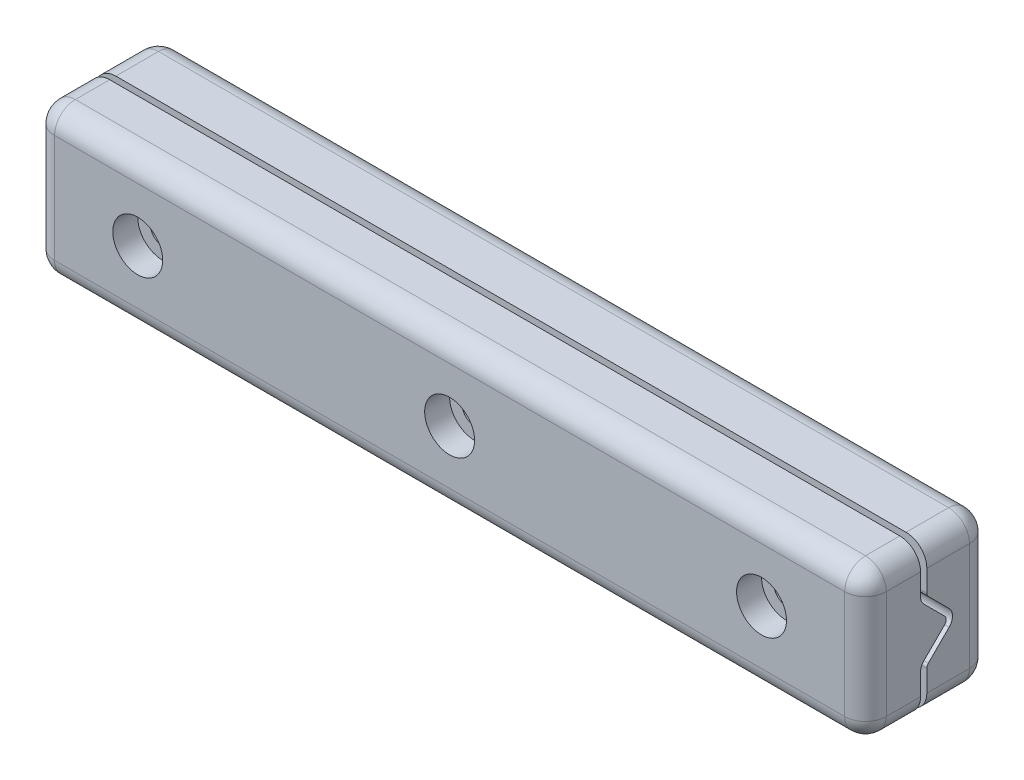
SolidWorks part; units mm, degrees
ref_plane "Спереди" through (0, 0, 0) normal (0, 0, 1) x (1, 0, 0)
ref_plane "Сверху" through (0, 0, 0) normal (0, 1, 0) x (1, 0, 0)
ref_plane "Справа" through (0, 0, 0) normal (1, 0, 0) x (0, 0, -1)
sketch "Эскиз1" plane through (0, 0, -1) normal (0, 0, 1) x (1, 0, 0)
  line L1 (303, -18) -> (503, -18)
  line L2 (303, -18) -> (303, 18)
  line L3 (303, 18) -> (503, 18)
  line L4 (503, -18) -> (503, 18)
  line L5 (403, 18) -> (403, -18) construction
  line L6 (303, 0) -> (503, 0) construction
  line L8 (500, 8.2426) -> (500, 15) construction
  line L9 (-460, 15) -> (500, 15) construction
  point P0 (403, 0)
  dimension "D3" = 200
  dimension "D1" = 3
  dimension "D2" = 3
extrude "Бобышка-Вытянуть1" add sketch "Эскиз1" along normal mid plane 30
fillet "Скругление1" radius 5 12 edges at (403, -18, -16) (303, -18, -1) (303, 0, -16) (503, -18, -1) (503, 0, -16) (403, -18, 14) (303, 0, 14) (503, 0, 14) (503, 18, -1) (403, 18, 14) (303, 18, -1) (403, 18, -16)
sketch "Эскиз3" plane through (503, 0, 0) normal (1, 0, 0) x (0, 0, -1)
  line L54 (0.0555, 5.8839) -> (5.0555, 0.8839)
  line L55 (5.0555, -0.8839) -> (0.0555, -5.8839)
  line L56 (-0.75, -7.8284) -> (-0.75, -15)
  line L57 (-0.75, -15) -> (0.75, -15)
  line L58 (0.75, -15) -> (0.75, -7.8284)
  line L59 (1.1161, -6.9445) -> (6.1161, -1.9445)
  line L60 (6.1161, 1.9445) -> (1.1161, 6.9445)
  line L61 (0.75, 7.8284) -> (0.75, 15)
  line L62 (0.75, 15) -> (-0.75, 15)
  line L63 (-0.75, 15) -> (-0.75, 7.8284)
  line L64 (0.0555, 5.8839) -> (5.0555, 0.8839)
  line L65 (5.0555, -0.8839) -> (0.0555, -5.8839)
  line L66 (-0.75, -7.8284) -> (-0.75, -19.2901)
  line L67 (-0.75, -19.2901) -> (0.75, -19.2901)
  line L68 (0.75, -19.2901) -> (0.75, -7.8284)
  line L69 (1.1161, -6.9445) -> (6.1161, -1.9445)
  line L70 (6.1161, 1.9445) -> (1.1161, 6.9445)
  line L71 (0.75, 7.8284) -> (0.75, 19.7741)
  line L72 (0.75, 19.7741) -> (-0.75, 19.7741)
  line L73 (-0.75, 19.7741) -> (-0.75, 7.8284)
  arc A22 (5.0555, -0.8839) -> (5.0555, 0.8839) centre (4.1716, 0) ccw
  arc A23 (0.0555, -5.8839) -> (-0.75, -7.8284) centre (2, -7.8284) ccw
  arc A24 (1.1161, -6.9445) -> (0.75, -7.8284) centre (2, -7.8284) ccw
  arc A25 (6.1161, -1.9445) -> (6.1161, 1.9445) centre (4.1716, 0) ccw
  arc A26 (0.75, 7.8284) -> (1.1161, 6.9445) centre (2, 7.8284) ccw
  arc A27 (-0.75, 7.8284) -> (0.0555, 5.8839) centre (2, 7.8284) ccw
  arc A28 (5.0555, -0.8839) -> (5.0555, 0.8839) centre (4.1716, 0) ccw
  arc A29 (0.0555, -5.8839) -> (-0.75, -7.8284) centre (2, -7.8284) ccw
  arc A30 (1.1161, -6.9445) -> (0.75, -7.8284) centre (2, -7.8284) ccw
  arc A31 (6.1161, -1.9445) -> (6.1161, 1.9445) centre (4.1716, 0) ccw
  arc A32 (0.75, 7.8284) -> (1.1161, 6.9445) centre (2, 7.8284) ccw
  arc A33 (-0.75, 7.8284) -> (0.0555, 5.8839) centre (2, 7.8284) ccw
  point P0 (0, 20.4335)
  point P24 (0, 0)
  point P26 (0, 0)
  point P28 (0, 0)
  dimension "D1" = 0
sketch "Эскиз4" plane through (0, 0, 14) normal (0, 0, 1) x (1, 0, 0)
  line L0 (328, 0) -> (403, 0) construction
  line L3 (403, 0) -> (478, 0) construction
  line L4 (403, 13) -> (403, -13) construction
  line L5 (498, 13) -> (308, 13) construction
  line L6 (308, -13) -> (498, -13) construction
  circle A0 centre (403, 0) radius 3
  circle A1 centre (328, 0) radius 3
  circle A2 centre (478, 0) radius 3
  dimension "D1" = 6
  dimension "D2" = 75
extrude "Вырез-Вытянуть8" cut sketch "Эскиз3" against normal through all
extrude "Вырез-Вытянуть4" cut sketch "Эскиз4" against normal through all
sketch "Эскиз7" plane through (0, 0, 14) normal (0, 0, 1) x (1, 0, 0)
  circle A2 centre (328, 0) radius 6
  circle A3 centre (328, 0) radius 6
  circle A5 centre (403, 0) radius 6
  circle A6 centre (403, 0) radius 6
  circle A8 centre (478, 0) radius 6
  circle A9 centre (478, 0) radius 6
  dimension "D2" = 3
  dimension "D3" = 3
extrude "Вырез-Вытянуть5" cut sketch "Эскиз7" against normal blind 6
sketch "Эскиз8" plane through (0, 0, -16) normal (0, 0, -1) x (-1, 0, 0)
  circle A2 centre (-328, 0) radius 6
  circle A3 centre (-328, 0) radius 6
  circle A5 centre (-403, 0) radius 6
  circle A6 centre (-403, 0) radius 6
  circle A8 centre (-478, 0) radius 6
  circle A9 centre (-478, 0) radius 6
  dimension "D2" = 3
  dimension "D3" = 3
extrude "Вырез-Вытянуть6" cut sketch "Эскиз8" against normal blind 6
equation "\"длина лезвия\"=1000"
equation "\"радиус острия\"=3"
equation "\"длина острия\"=40"
equation "\"ширина лезвия\"=30"
equation "\"радиус сгиба\"=2"
equation "\"высота ребра жесткости\"=7"
equation "\"толщина лезвия \"=2"
equation "\"длина рукоятки\"=200"
equation "\"тлщина рукоятки\"=30"
equation "\"диаметр заклепки\"=6"
equation "\"расстояние между заклнпками\"=75"
equation "\"глубина заклепки\"=6"
equation "\"отступ от заклепки\"=3"
equation "\"диаметр шляпы\"=\"диаметр заклепки\" + 2*\"отступ от заклепки\""
equation "\"D2@Эскиз1\"=\"отступ от заклепки\""
equation "\"D1@Эскиз1\"=\"отступ от заклепки\""
equation "\"D3@Эскиз1\"=\"длина рукоятки\""
equation "\"D1@Эскиз4\"=\"диаметр заклепки\""
equation "\"D2@Эскиз4\"=\"расстояние между заклнпками\""
equation "\"D1@Эскиз7\"=\"отступ от заклепки\""
equation "\"D2@Эскиз7\"=\"отступ от заклепки\""
equation "\"D3@Эскиз7\"=\"отступ от заклепки\""
equation "\"D1@Бобышка-Вытянуть1\"=\"тлщина рукоятки\""
equation "\"D1@Вырез-Вытянуть5\"=\"глубина заклепки\""
equation "\"радиус скруглений\"=5"
equation "\"D1@Скругление1\"=\"радиус скруглений\""
equation "\"D1@Эскиз8\"=\"отступ от заклепки\""
equation "\"D2@Эскиз8\"=\"отступ от заклепки\""
equation "\"D3@Эскиз8\"=\"отступ от заклепки\""
equation "\"D1@Вырез-Вытянуть6\"=\"глубина заклепки\""
equation "\"высота головки\"=1.2"
equation "\"высота купола\"=3"
